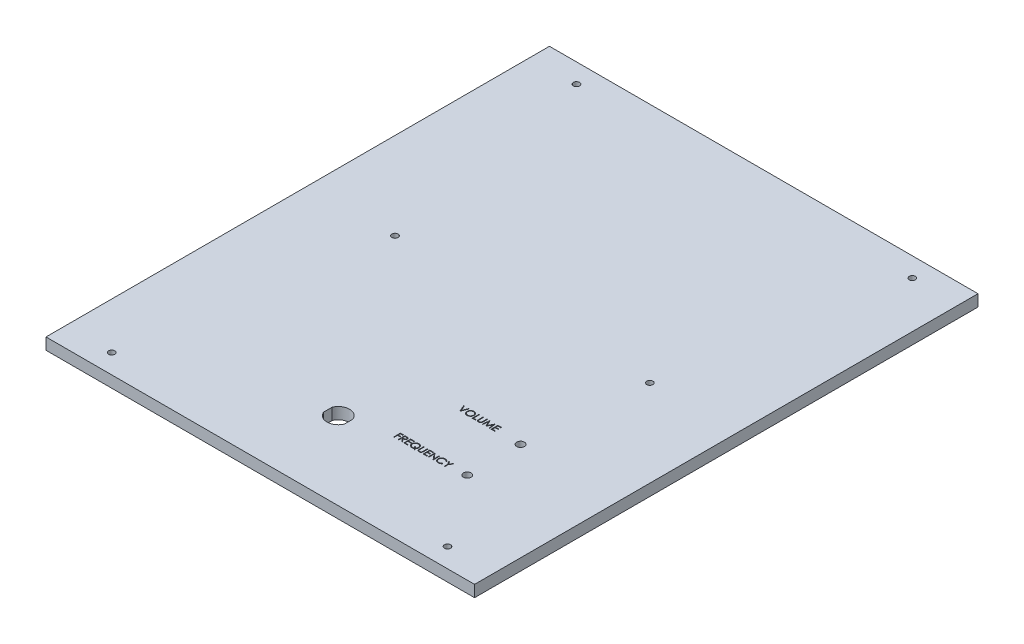
SolidWorks part; units mm, degrees
ref_plane "Front Plane" through (0, 0, 0) normal (0, 0, 1) x (1, 0, 0)
ref_plane "Top Plane" through (0, 0, 0) normal (0, 1, 0) x (1, 0, 0)
ref_plane "Right Plane" through (0, 0, 0) normal (1, 0, 0) x (0, 0, -1)
sketch "Sketch1" plane through (0, 0, 0) normal (0, 1, 0) x (1, 0, 0)
  line L0 (-111, 125.6127) -> (111, 125.6127)
  line L1 (-111, 125.6127) -> (-111, -125.6127)
  line L3 (111, 125.6127) -> (111, -125.6127)
  line L4 (-111, 125.6127) -> (111, -125.6127) construction
  line L5 (-111, -125.6127) -> (111, 125.6127) construction
  line L8 (-111, -125.6127) -> (-111, -165.6127)
  line L9 (-111, -165.6127) -> (111, -165.6127)
  line L10 (111, -125.6127) -> (111, -165.6127)
  point P10 (0, 0)
  dimension "D1" = 222
  dimension "D2" = 40
extrude "Boss-Extrude1" add sketch "Sketch1" along normal blind 6
sketch "Sketch2" plane through (0, 6, 0) normal (0, 1, 0) x (1, 0, 0)
  circle A0 centre (-57, 100.5142) radius 1.6
sketch "Sketch3" plane through (0, 0, 0) normal (0, -1, 0) x (1, 0, 0)
  line L0 (-111, -125.6127) -> (-111, 165.6127) construction
  line L1 (111, -125.6127) -> (-111, -125.6127)
  line L2 (111, -125.6127) -> (111, -95.1873)
  line L3 (111, -95.1873) -> (-111, -95.1873)
  line L4 (-111, -125.6127) -> (-111, -95.1873)
  circle A0 centre (-66, 29.8127) radius 1.6
  circle A1 centre (66, 29.8127) radius 1.6
  dimension "D1" = 3.2
extrude "Cut-Extrude1" cut sketch "Sketch3" against normal blind 10
sketch "Sketch4" plane through (0, 0, 0) normal (0, -1, 0) x (1, 0, 0)
  circle A0 centre (87, 155.6127) radius 1.6
  circle A1 centre (-87, 155.6127) radius 1.6
  circle A2 centre (-87, -85.1873) radius 1.6
  circle A3 centre (87, -85.1873) radius 1.6
extrude "Cut-Extrude2" cut sketch "Sketch4" against normal blind 10
sketch "Sketch5" plane through (0, 0, 0) normal (0, -1, 0) x (-1, 0, 0)
  line L0 (-5.375, -123.0201) -> (-5.375, -127.4052)
  line L1 (5.375, -123.0201) -> (5.375, -127.4052)
  arc A0 (-5.375, -127.4052) -> (5.375, -127.4052) centre (0, -125.2127) ccw
  arc A1 (5.375, -123.0201) -> (-5.375, -123.0201) centre (0, -125.2127) ccw
extrude "Cut-Extrude3" cut sketch "Sketch5" against normal blind 10
sketch "Sketch6" plane through (0, 0, 0) normal (0, -1, 0) x (1, 0, 0)
  circle A0 centre (60.0879, 90.8682) radius 2
  circle A1 centre (60.0879, 118.4814) radius 2
  dimension "D1" = 4
  dimension "D2" = 4
extrude "Cut-Extrude4" cut sketch "Sketch6" against normal blind 10
sketch "Sketch10" plane through (0, 6, 0) normal (0, 1, 0) x (1, 0, 0)
  text T0 "VOLUME"
  text T1 "FREQUENCY"
  point P2 (0, 0)
  point P3 (0, 0)
  point P4 (0, 0)
  point P5 (0, 0)
extrude "Cut-Extrude5" cut sketch "Sketch10" against normal blind 1
